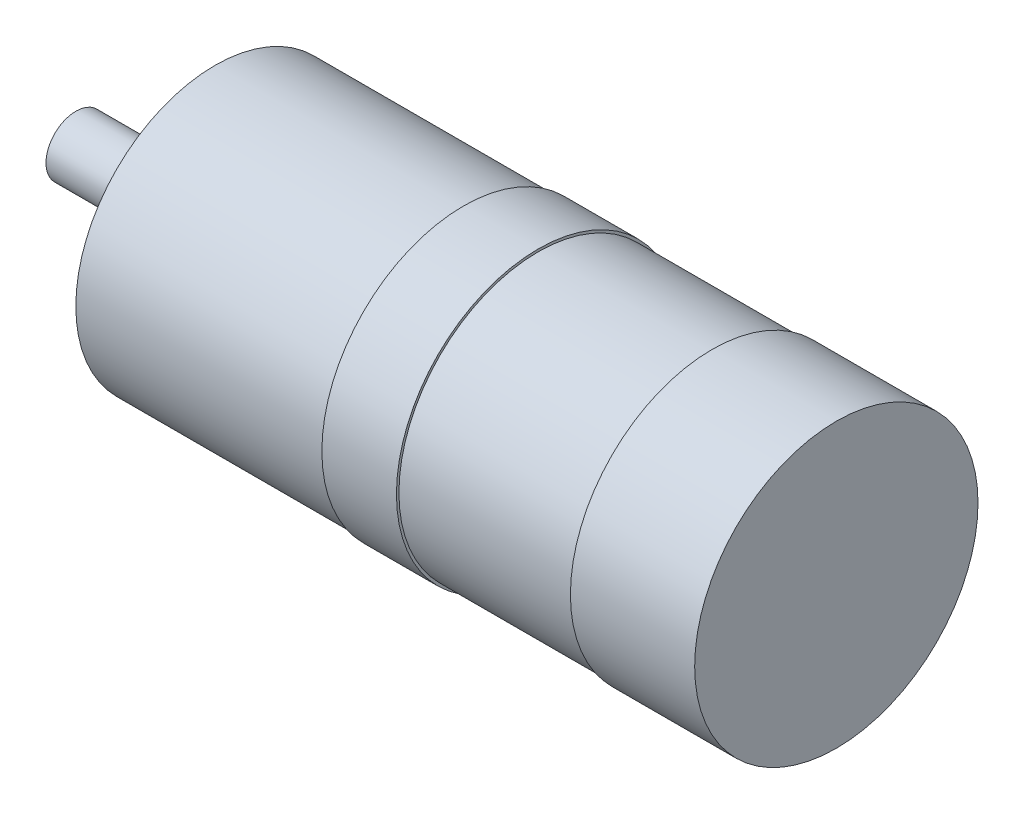
SolidWorks part; units mm, degrees
ref_plane "Front Plane" through (0, 0, 0) normal (0, 0, 1) x (1, 0, 0)
ref_plane "Top Plane" through (0, 0, 0) normal (0, 1, 0) x (1, 0, 0)
ref_plane "Right Plane" through (0, 0, 0) normal (1, 0, 0) x (0, 0, -1)
sketch "Sketch1" plane through (0, 0, 0) normal (0, 0, 1) x (1, 0, 0)
  line L0 (0, 0) -> (153, 0)
  line L1 (-903.2374, 0) -> (44258.6317, 0) construction
  line L2 (0, 0) -> (0, 6)
  line L3 (0, 6) -> (26, 6)
  line L4 (26, 6) -> (26, 16)
  line L5 (26, 16) -> (28, 16)
  line L6 (28, 16) -> (28, 28)
  line L7 (28, 28) -> (78, 28)
  line L8 (78, 28) -> (78, 28.5)
  line L9 (78, 28.5) -> (93, 28.5)
  line L10 (93, 28.5) -> (93, 28)
  line L11 (93, 28) -> (128, 28)
  line L12 (128, 28) -> (128, 28.5)
  line L13 (128, 28.5) -> (153, 28.5)
  line L14 (153, 28.5) -> (153, 0)
  point P1 (28, 22)
  point P6 (163.1628, 0)
  dimension "D2" = 28
  dimension "D3" = 2
  dimension "D4" = 32
  dimension "D5" = 56
  dimension "D6" = 57
  dimension "D7" = 125
  dimension "D8" = 75
  dimension "D9" = 15
  dimension "D10" = 25
  dimension "D11" = 12
revolve "Revolve1" add sketch "Sketch1" angle 360 about L1
sketch "Sketch2" plane through (28, 0, 0) normal (-1, 0, 0) x (0, 0, 1)
  circle A0 centre (0, 0) radius 22.5 construction
  circle A1 centre (-15.9099, 15.9099) radius 2.1
  circle A2 centre (15.9099, 15.9099) radius 2.1
  circle A3 centre (15.9099, -15.9099) radius 2.1
  circle A4 centre (-15.9099, -15.9099) radius 2.1
  point P5 (26.9369, 19.1042)
  point P6 (0, 0)
  point P7 (0, 0)
  point P14 (0, 0)
  dimension "D1" = 45
  dimension "D3" = 4.2
  dimension "D2" = 4
extrude "Cut-Extrude1" cut sketch "Sketch2" against normal blind 6.5
